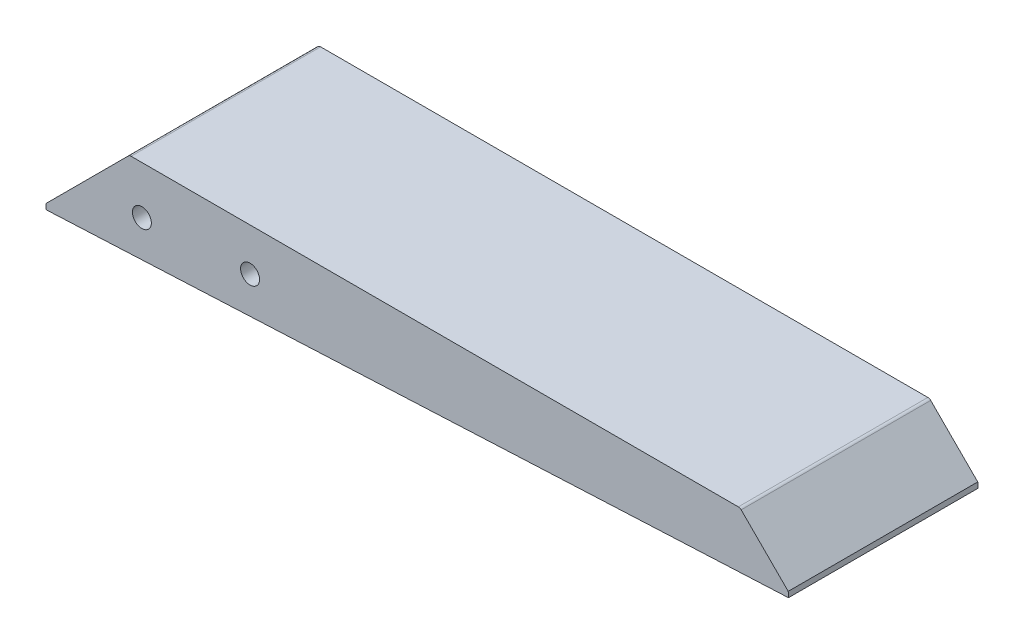
SolidWorks part; units mm, degrees
ref_plane "前视基准面" through (0, 0, 0) normal (0, 0, 1) x (1, 0, 0)
ref_plane "上视基准面" through (0, 0, 0) normal (0, 1, 0) x (1, 0, 0)
ref_plane "右视基准面" through (0, 0, 0) normal (1, 0, 0) x (0, 0, -1)
other "Configuration Table"
sketch "草图1" plane through (0, 0, 0) normal (0, 0, 1) x (1, 0, 0)
  line L0 (166.8324, 7.5944) -> (168.9537, 9.7157) construction
  line L1 (168.9537, 9.7157) -> (160.2639, 18.4056) construction
  line L2 (158.1425, 16.2843) -> (166.8324, 7.5944) construction
  line L3 (157.6217, 19.5) -> (45.4745, 19.5) construction
  line L4 (45.4745, 16.5) -> (157.6217, 16.5) construction
  line L5 (29.7639, 1.0944) -> (44.9537, 16.2843) construction
  line L6 (42.8324, 18.4056) -> (27.6425, 3.2157) construction
  line L7 (27.6425, 3.2157) -> (29.7639, 1.0944) construction
  line L8 (166.8324, 7.5944) -> (168.9537, 9.7157)
  line L9 (168.9537, 9.7157) -> (160.2639, 18.4056)
  line L10 (158.1425, 16.2843) -> (166.8324, 7.5944)
  line L11 (157.6217, 19.5) -> (45.4745, 19.5)
  line L12 (45.4745, 16.5) -> (157.6217, 16.5)
  line L13 (29.7639, 1.0944) -> (44.9537, 16.2843)
  line L14 (42.8324, 18.4056) -> (27.6425, 3.2157)
  line L15 (27.6425, 3.2157) -> (29.7639, 1.0944)
  line L16 (29.7639, 1.0944) -> (166.8324, 7.5944)
  arc A0 (158.1425, 16.2843) -> (157.6217, 16.5) centre (157.6217, 15.7634) ccw construction
  arc A1 (160.2639, 18.4056) -> (157.6217, 19.5) centre (157.6217, 15.7634) ccw construction
  arc A2 (45.4745, 16.5) -> (44.9537, 16.2843) centre (45.4745, 15.7634) ccw construction
  arc A3 (45.4745, 19.5) -> (42.8324, 18.4056) centre (45.4745, 15.7634) ccw construction
  arc A4 (158.1425, 16.2843) -> (157.6217, 16.5) centre (157.6217, 15.7634) ccw
  arc A5 (160.2639, 18.4056) -> (157.6217, 19.5) centre (157.6217, 15.7634) ccw
  arc A6 (45.4745, 16.5) -> (44.9537, 16.2843) centre (45.4745, 15.7634) ccw
  arc A7 (45.4745, 19.5) -> (42.8324, 18.4056) centre (45.4745, 15.7634) ccw
extrude "凸台-拉伸1" add sketch "草图1" against normal blind 35 contours L12 A6 L13 L16 L10 A4 region at (94.8139, 10.1061, 0)
sketch "草图2" plane through (0.015, -0.3163, 0) normal (0.0474, -0.9989, 0) x (0.9989, 0.0474, 0)
  line L0 (165.5048, -1.5) -> (31.2823, -1.5)
  line L1 (31.2823, -1.5) -> (31.2823, -33.5)
  line L2 (31.2823, -33.5) -> (165.5048, -33.5)
  line L3 (165.5048, -33.5) -> (165.5048, -1.5)
  line L4 (167.0048, 0) -> (29.7823, 0)
  line L5 (29.7823, 0) -> (29.7823, -35)
  line L6 (29.7823, -35) -> (167.0048, -35)
  line L7 (167.0048, -35) -> (167.0048, 0)
  line L8 (167.0048, 0) -> (29.7823, 0)
  line L9 (29.7823, 0) -> (29.7823, -35)
  line L10 (29.7823, -35) -> (167.0048, -35)
  line L11 (167.0048, -35) -> (167.0048, 0)
  dimension "D1" = 0
  dimension "D2" = 1.5
extrude "凸台-拉伸2" add sketch "草图2" along normal blind 1
fillet "圆角1" radius 2 4 edges at (31.2859, 0.666, -33.5) (165.3577, 7.0239, -33.5) (165.3577, 7.0239, -1.5) (31.2859, 0.666, -1.5)
sketch "草图3" plane through (0, 0, 0) normal (0, 0, 1) x (1, 0, 0)
  line L0 (166.8797, 6.5955) -> (29.8112, 0.0955) construction
  line L1 (29.8112, 0.0955) -> (29.7639, 1.0944) construction
  circle A0 centre (47.4713, 7.6906) radius 1.75
  circle A1 centre (67.4487, 8.6414) radius 1.75
  dimension "D1" = 3.5
  dimension "D3" = 20
  dimension "D4" = 6.75
  dimension "D5" = 18
  dimension "D2" = 2
extrude "切除-拉伸1" cut sketch "草图3" against normal blind 6.2
sketch "草图4" plane through (0, 0, -35) normal (0, 0, -1) x (-1, 0, 0)
  circle A0 centre (-47.4713, 7.6906) radius 1.75 construction
  circle A1 centre (-67.4487, 8.6414) radius 1.75 construction
  circle A2 centre (-47.4713, 7.6906) radius 1.75
  circle A3 centre (-67.4487, 8.6414) radius 1.75
extrude "切除-拉伸2" cut sketch "草图4" against normal blind 6.55
sketch "草图6" plane through (0.015, -0.3163, 0) normal (0.0474, -0.9989, 0) x (0.9989, 0.0474, 0)
  line L1199 (144.5332, -18.3417) -> (144.2984, -18.2008)
  line L1200 (144.2984, -18.2008) -> (143.9227, -18.2947)
  line L1201 (143.9227, -18.2947) -> (142.7956, -19.4688)
  line L1202 (142.7956, -19.4688) -> (142.279, -19.8915)
  line L1203 (142.279, -19.8915) -> (142.1381, -19.8915)
  line L1204 (142.1381, -19.8915) -> (142.0911, -19.7506)
  line L1205 (142.0911, -19.7506) -> (142.6547, -18.2478)
  line L1206 (142.6547, -18.2478) -> (142.7016, -17.8251)
  line L1207 (142.7016, -17.8251) -> (142.4668, -17.4963)
  line L1208 (142.4668, -17.4963) -> (141.9972, -17.4494)
  line L1209 (141.9972, -17.4494) -> (141.6684, -17.7312)
  line L1210 (141.6684, -17.7312) -> (141.2457, -18.3887)
  line L1211 (141.2457, -18.3887) -> (140.2595, -19.3749)
  line L1212 (140.2595, -19.3749) -> (139.2263, -20.1263)
  line L1213 (139.2263, -20.1263) -> (138.8036, -20.3142)
  line L1214 (138.8036, -20.3142) -> (138.6157, -20.3142)
  line L1215 (138.6157, -20.3142) -> (138.5218, -20.2203)
  line L1216 (138.5218, -20.2203) -> (138.5218, -19.9854)
  line L1217 (138.5218, -19.9854) -> (138.6627, -19.6097)
  line L1218 (138.6627, -19.6097) -> (139.4611, -18.4356)
  line L1219 (139.4611, -18.4356) -> (139.4611, -18.1069)
  line L1220 (139.4611, -18.1069) -> (139.2732, -17.872)
  line L1221 (139.2732, -17.872) -> (139.0384, -17.7781)
  line L1222 (139.0384, -17.7781) -> (138.6627, -17.872)
  line L1223 (138.6627, -17.872) -> (138.0052, -18.6235)
  line L1224 (138.0052, -18.6235) -> (137.5825, -19.3279)
  line L1225 (137.5825, -19.3279) -> (137.3477, -20.1263)
  line L1226 (137.3477, -20.1263) -> (137.3477, -20.4081)
  line L1227 (137.3477, -20.4081) -> (137.4886, -20.7838)
  line L1228 (137.4886, -20.7838) -> (137.9113, -21.1595)
  line L1229 (137.9113, -21.1595) -> (138.1931, -21.2535)
  line L1230 (138.1931, -21.2535) -> (138.7566, -21.2535)
  line L1231 (138.7566, -21.2535) -> (139.6959, -20.8778)
  line L1232 (139.6959, -20.8778) -> (140.6352, -20.1733)
  line L1233 (140.6352, -20.1733) -> (140.7761, -20.2203)
  line L1234 (140.7761, -20.2203) -> (140.6352, -20.8308)
  line L1235 (140.6352, -20.8308) -> (140.5413, -20.9247)
  line L1236 (140.5413, -20.9247) -> (138.5218, -21.817)
  line L1237 (138.5218, -21.817) -> (137.9582, -22.1928)
  line L1238 (137.9582, -22.1928) -> (137.6295, -22.5215)
  line L1239 (137.6295, -22.5215) -> (137.4416, -22.8503)
  line L1240 (137.4416, -22.8503) -> (137.4416, -23.2729)
  line L1241 (137.4416, -23.2729) -> (137.6765, -23.6487)
  line L1242 (137.6765, -23.6487) -> (138.0052, -23.8835)
  line L1243 (138.0052, -23.8835) -> (138.3809, -24.0244)
  line L1244 (138.3809, -24.0244) -> (139.1793, -24.0713)
  line L1245 (139.1793, -24.0713) -> (139.8368, -23.8835)
  line L1246 (139.8368, -23.8835) -> (140.4473, -23.5078)
  line L1247 (140.4473, -23.5078) -> (141.0109, -22.8503)
  line L1248 (141.0109, -22.8503) -> (141.4806, -21.817)
  line L1249 (141.4806, -21.817) -> (141.6215, -21.3004)
  line L1250 (141.6215, -21.3004) -> (142.8425, -20.596)
  line L1251 (142.8425, -20.596) -> (143.7348, -19.8445)
  line L1252 (143.7348, -19.8445) -> (144.4863, -18.9522)
  line L1253 (144.4863, -18.9522) -> (144.5802, -18.7644)
  line L1254 (144.5802, -18.7644) -> (144.5332, -18.3417)
  line L1255 (140.2125, -21.9579) -> (140.2125, -22.0988)
  line L1256 (140.2125, -22.0988) -> (140.0247, -22.4745)
  line L1257 (140.0247, -22.4745) -> (139.555, -22.9912)
  line L1258 (139.555, -22.9912) -> (139.0854, -23.226)
  line L1259 (139.0854, -23.226) -> (138.6627, -23.226)
  line L1260 (138.6627, -23.226) -> (138.5218, -23.0851)
  line L1261 (138.5218, -23.0851) -> (138.5688, -22.8503)
  line L1262 (138.5688, -22.8503) -> (138.8036, -22.5685)
  line L1263 (138.8036, -22.5685) -> (140.0716, -21.911)
  line L1264 (140.0716, -21.911) -> (140.2125, -21.9579)
  line L1265 (156.9788, -14.8663) -> (156.744, -14.7254)
  line L1266 (156.744, -14.7254) -> (156.4152, -14.7254)
  line L1267 (156.4152, -14.7254) -> (156.1334, -14.9133)
  line L1268 (156.1334, -14.9133) -> (156.0395, -15.1481)
  line L1269 (156.0395, -15.1481) -> (155.9925, -16.0874)
  line L1270 (155.9925, -16.0874) -> (155.5698, -17.1676)
  line L1271 (155.5698, -17.1676) -> (154.7715, -18.3417)
  line L1272 (154.7715, -18.3417) -> (153.9731, -19.0462)
  line L1273 (153.9731, -19.0462) -> (153.6913, -18.9992)
  line L1274 (153.6913, -18.9992) -> (153.6913, -18.3417)
  line L1275 (153.6913, -18.3417) -> (153.8791, -17.7312)
  line L1276 (153.8791, -17.7312) -> (153.8791, -17.3085)
  line L1277 (153.8791, -17.3085) -> (153.6913, -17.0736)
  line L1278 (153.6913, -17.0736) -> (153.5034, -16.9797)
  line L1279 (153.5034, -16.9797) -> (153.2686, -16.9797)
  line L1280 (153.2686, -16.9797) -> (153.0338, -17.0736)
  line L1281 (153.0338, -17.0736) -> (152.8459, -17.2615)
  line L1282 (152.8459, -17.2615) -> (152.3763, -18.1069)
  line L1283 (152.3763, -18.1069) -> (151.39, -19.1401)
  line L1284 (151.39, -19.1401) -> (151.1082, -19.3279)
  line L1285 (151.1082, -19.3279) -> (150.9204, -19.281)
  line L1286 (150.9204, -19.281) -> (150.9673, -18.9053)
  line L1287 (150.9673, -18.9053) -> (151.2022, -18.2478)
  line L1288 (151.2022, -18.2478) -> (152.0006, -16.7919)
  line L1289 (152.0006, -16.7919) -> (151.9536, -16.3692)
  line L1290 (151.9536, -16.3692) -> (151.5779, -16.1344)
  line L1291 (151.5779, -16.1344) -> (151.2022, -16.2283)
  line L1292 (151.2022, -16.2283) -> (150.9204, -16.5101)
  line L1293 (150.9204, -16.5101) -> (150.122, -17.872)
  line L1294 (150.122, -17.872) -> (149.8872, -18.6235)
  line L1295 (149.8872, -18.6235) -> (149.0418, -19.4219)
  line L1296 (149.0418, -19.4219) -> (148.4782, -19.8445)
  line L1297 (148.4782, -19.8445) -> (148.2434, -19.9385)
  line L1298 (148.2434, -19.9385) -> (147.9616, -19.9385)
  line L1299 (147.9616, -19.9385) -> (147.7268, -19.7976)
  line L1300 (147.7268, -19.7976) -> (147.3511, -19.4219)
  line L1301 (147.3511, -19.4219) -> (147.3511, -19.281)
  line L1302 (147.3511, -19.281) -> (149.1827, -17.5433)
  line L1303 (149.1827, -17.5433) -> (149.2766, -17.3554)
  line L1304 (149.2766, -17.3554) -> (149.2766, -17.1206)
  line L1305 (149.2766, -17.1206) -> (149.0418, -16.8388)
  line L1306 (149.0418, -16.8388) -> (148.6661, -16.7919)
  line L1307 (148.6661, -16.7919) -> (148.3373, -16.9328)
  line L1308 (148.3373, -16.9328) -> (146.6466, -18.4826)
  line L1309 (146.6466, -18.4826) -> (146.5057, -18.4826)
  line L1310 (146.5057, -18.4826) -> (145.6604, -17.5433)
  line L1311 (145.6604, -17.5433) -> (145.1907, -17.4963)
  line L1312 (145.1907, -17.4963) -> (145.0029, -17.5903)
  line L1313 (145.0029, -17.5903) -> (144.815, -17.8251)
  line L1314 (144.815, -17.8251) -> (144.815, -18.1069)
  line L1315 (144.815, -18.1069) -> (145.7543, -19.281)
  line L1316 (145.7543, -19.281) -> (145.7543, -19.3749)
  line L1317 (145.7543, -19.3749) -> (144.1106, -21.2065)
  line L1318 (144.1106, -21.2065) -> (143.9227, -21.5822)
  line L1319 (143.9227, -21.5822) -> (143.9697, -21.864)
  line L1320 (143.9697, -21.864) -> (144.2515, -22.0988)
  line L1321 (144.2515, -22.0988) -> (144.5802, -22.0988)
  line L1322 (144.5802, -22.0988) -> (144.815, -22.0049)
  line L1323 (144.815, -22.0049) -> (146.4588, -20.2203)
  line L1324 (146.4588, -20.2203) -> (146.5997, -20.2203)
  line L1325 (146.5997, -20.2203) -> (147.0693, -20.6429)
  line L1326 (147.0693, -20.6429) -> (147.492, -20.8778)
  line L1327 (147.492, -20.8778) -> (148.2904, -20.9247)
  line L1328 (148.2904, -20.9247) -> (149.0888, -20.549)
  line L1329 (149.0888, -20.549) -> (149.7463, -19.9385)
  line L1330 (149.7463, -19.9385) -> (149.8872, -19.9385)
  line L1331 (149.8872, -19.9385) -> (150.169, -20.2672)
  line L1332 (150.169, -20.2672) -> (150.4038, -20.4081)
  line L1333 (150.4038, -20.4081) -> (150.9204, -20.4551)
  line L1334 (150.9204, -20.4551) -> (151.2491, -20.3611)
  line L1335 (151.2491, -20.3611) -> (151.8127, -20.0324)
  line L1336 (151.8127, -20.0324) -> (152.5172, -19.3749)
  line L1337 (152.5172, -19.3749) -> (152.6581, -19.4219)
  line L1338 (152.6581, -19.4219) -> (152.752, -19.6567)
  line L1339 (152.752, -19.6567) -> (153.0338, -19.9385)
  line L1340 (153.0338, -19.9385) -> (153.4565, -20.1263)
  line L1341 (153.4565, -20.1263) -> (154.067, -20.0794)
  line L1342 (154.067, -20.0794) -> (154.5366, -19.8915)
  line L1343 (154.5366, -19.8915) -> (155.2881, -19.3279)
  line L1344 (155.2881, -19.3279) -> (155.7577, -18.8583)
  line L1345 (155.7577, -18.8583) -> (156.2743, -18.1538)
  line L1346 (156.2743, -18.1538) -> (156.744, -17.3085)
  line L1347 (156.744, -17.3085) -> (157.1197, -16.0404)
  line L1348 (157.1197, -16.0404) -> (157.1197, -15.1951)
  line L1349 (157.1197, -15.1951) -> (156.9788, -14.8663)
  line L1599 (103.178, -10.8157) -> (102.5205, -10.4869)
  line L1600 (102.5205, -10.4869) -> (101.7221, -10.2521)
  line L1601 (101.7221, -10.2521) -> (100.2192, -10.2521)
  line L1602 (100.2192, -10.2521) -> (99.5148, -10.5339)
  line L1603 (99.5148, -10.5339) -> (99.0921, -10.8626)
  line L1604 (99.0921, -10.8626) -> (97.4014, -11.6141)
  line L1605 (97.4014, -11.6141) -> (95.8985, -12.1307)
  line L1606 (95.8985, -12.1307) -> (94.8653, -12.2716)
  line L1607 (94.8653, -12.2716) -> (94.6305, -12.4594)
  line L1608 (94.6305, -12.4594) -> (94.5365, -12.6473)
  line L1609 (94.5365, -12.6473) -> (94.5835, -12.9291)
  line L1610 (94.5835, -12.9291) -> (95.0531, -13.3987)
  line L1611 (95.0531, -13.3987) -> (95.4289, -13.5866)
  line L1612 (95.4289, -13.5866) -> (96.0864, -13.7744)
  line L1613 (96.0864, -13.7744) -> (97.6362, -13.7744)
  line L1614 (97.6362, -13.7744) -> (97.824, -14.1032)
  line L1615 (97.824, -14.1032) -> (97.871, -14.9955)
  line L1616 (97.871, -14.9955) -> (97.7771, -15.3242)
  line L1617 (97.7771, -15.3242) -> (96.556, -15.7939)
  line L1618 (96.556, -15.7939) -> (95.8046, -16.2635)
  line L1619 (95.8046, -16.2635) -> (94.9592, -15.9817)
  line L1620 (94.9592, -15.9817) -> (94.4896, -15.9817)
  line L1621 (94.4896, -15.9817) -> (94.1608, -16.1226)
  line L1622 (94.1608, -16.1226) -> (94.0199, -16.2635)
  line L1623 (94.0199, -16.2635) -> (93.926, -16.5453)
  line L1624 (93.926, -16.5453) -> (94.2078, -17.4846)
  line L1625 (94.2078, -17.4846) -> (94.2548, -18.8935)
  line L1626 (94.2548, -18.8935) -> (94.3956, -19.7389)
  line L1627 (94.3956, -19.7389) -> (94.6305, -20.3964)
  line L1628 (94.6305, -20.3964) -> (94.9123, -20.866)
  line L1629 (94.9123, -20.866) -> (95.4758, -21.4296)
  line L1630 (95.4758, -21.4296) -> (95.9924, -21.6644)
  line L1631 (95.9924, -21.6644) -> (96.603, -21.7114)
  line L1632 (96.603, -21.7114) -> (97.3544, -21.4766)
  line L1633 (97.3544, -21.4766) -> (97.5423, -21.4766)
  line L1634 (97.5423, -21.4766) -> (97.5892, -21.6644)
  line L1635 (97.5892, -21.6644) -> (97.4483, -22.3219)
  line L1636 (97.4483, -22.3219) -> (97.2605, -22.7916)
  line L1637 (97.2605, -22.7916) -> (96.7908, -23.3551)
  line L1638 (96.7908, -23.3551) -> (95.1471, -23.8248)
  line L1639 (95.1471, -23.8248) -> (93.6442, -24.1066)
  line L1640 (93.6442, -24.1066) -> (92.7519, -24.1535)
  line L1641 (92.7519, -24.1535) -> (92.4701, -24.2944)
  line L1642 (92.4701, -24.2944) -> (92.1883, -24.6232)
  line L1643 (92.1883, -24.6232) -> (92.0944, -25.0928)
  line L1644 (92.0944, -25.0928) -> (92.3292, -25.6564)
  line L1645 (92.3292, -25.6564) -> (92.7519, -26.0791)
  line L1646 (92.7519, -26.0791) -> (93.4094, -26.4548)
  line L1647 (93.4094, -26.4548) -> (93.973, -26.6426)
  line L1648 (93.973, -26.6426) -> (95.5228, -26.6426)
  line L1649 (95.5228, -26.6426) -> (96.4621, -26.4078)
  line L1650 (96.4621, -26.4078) -> (100.5949, -24.905)
  line L1651 (100.5949, -24.905) -> (102.9431, -24.2005)
  line L1652 (102.9431, -24.2005) -> (103.3658, -24.2475)
  line L1653 (103.3658, -24.2475) -> (103.9764, -25.2807)
  line L1654 (103.9764, -25.2807) -> (104.446, -25.7034)
  line L1655 (104.446, -25.7034) -> (104.9156, -25.9382)
  line L1656 (104.9156, -25.9382) -> (105.3853, -26.0321)
  line L1657 (105.3853, -26.0321) -> (105.9019, -25.9851)
  line L1658 (105.9019, -25.9851) -> (106.4185, -25.7503)
  line L1659 (106.4185, -25.7503) -> (106.7942, -25.3746)
  line L1660 (106.7942, -25.3746) -> (107.029, -24.7641)
  line L1661 (107.029, -24.7641) -> (107.029, -24.2005)
  line L1662 (107.029, -24.2005) -> (106.8881, -23.6839)
  line L1663 (106.8881, -23.6839) -> (106.5594, -23.1203)
  line L1664 (106.5594, -23.1203) -> (105.8549, -22.3689)
  line L1665 (105.8549, -22.3689) -> (104.9156, -21.7114)
  line L1666 (104.9156, -21.7114) -> (103.8824, -21.2417)
  line L1667 (103.8824, -21.2417) -> (103.178, -21.0539)
  line L1668 (103.178, -21.0539) -> (102.6144, -21.1009)
  line L1669 (102.6144, -21.1009) -> (102.4265, -21.1948)
  line L1670 (102.4265, -21.1948) -> (102.2387, -21.4766)
  line L1671 (102.2387, -21.4766) -> (102.3326, -21.8523)
  line L1672 (102.3326, -21.8523) -> (102.6144, -22.181)
  line L1673 (102.6144, -22.181) -> (102.5205, -22.3689)
  line L1674 (102.5205, -22.3689) -> (101.2524, -22.5567)
  line L1675 (101.2524, -22.5567) -> (100.2662, -22.7916)
  line L1676 (100.2662, -22.7916) -> (99.9374, -22.7446)
  line L1677 (99.9374, -22.7446) -> (99.9374, -22.6037)
  line L1678 (99.9374, -22.6037) -> (100.2662, -21.9462)
  line L1679 (100.2662, -21.9462) -> (100.5949, -20.7721)
  line L1680 (100.5949, -20.7721) -> (100.7358, -20.6782)
  line L1681 (100.7358, -20.6782) -> (101.5342, -20.4903)
  line L1682 (101.5342, -20.4903) -> (102.8492, -20.3494)
  line L1683 (102.8492, -20.3494) -> (103.5067, -20.1146)
  line L1684 (103.5067, -20.1146) -> (103.8355, -19.7859)
  line L1685 (103.8355, -19.7859) -> (103.9764, -19.4571)
  line L1686 (103.9764, -19.4571) -> (104.5399, -18.6587)
  line L1687 (104.5399, -18.6587) -> (105.3383, -17.015)
  line L1688 (105.3383, -17.015) -> (105.3383, -16.3575)
  line L1689 (105.3383, -16.3575) -> (105.2444, -16.0757)
  line L1690 (105.2444, -16.0757) -> (105.0096, -15.7)
  line L1691 (105.0096, -15.7) -> (104.1642, -14.9955)
  line L1692 (104.1642, -14.9955) -> (103.6006, -14.7137)
  line L1693 (103.6006, -14.7137) -> (102.5674, -14.4319)
  line L1694 (102.5674, -14.4319) -> (101.5812, -14.4319)
  line L1695 (101.5812, -14.4319) -> (101.2524, -14.5259)
  line L1696 (101.2524, -14.5259) -> (100.8298, -14.4789)
  line L1697 (100.8298, -14.4789) -> (100.7828, -13.9623)
  line L1698 (100.7828, -13.9623) -> (100.6889, -13.7744)
  line L1699 (100.6889, -13.7744) -> (100.6889, -13.6335)
  line L1700 (100.6889, -13.6335) -> (100.7828, -13.5396)
  line L1701 (100.7828, -13.5396) -> (103.2249, -12.9291)
  line L1702 (103.2249, -12.9291) -> (103.7885, -12.4594)
  line L1703 (103.7885, -12.4594) -> (103.9294, -12.1307)
  line L1704 (103.9294, -12.1307) -> (103.8824, -11.6141)
  line L1705 (103.8824, -11.6141) -> (103.7415, -11.3323)
  line L1706 (103.7415, -11.3323) -> (103.178, -10.8157)
  line L1707 (97.7301, -17.2967) -> (97.7301, -19.3162)
  line L1708 (97.7301, -19.3162) -> (97.4014, -19.551)
  line L1709 (97.4014, -19.551) -> (96.8848, -19.598)
  line L1710 (96.8848, -19.598) -> (96.6969, -19.4571)
  line L1711 (96.6969, -19.4571) -> (96.556, -19.0344)
  line L1712 (96.556, -19.0344) -> (96.509, -17.9073)
  line L1713 (96.509, -17.9073) -> (96.6499, -17.7664)
  line L1714 (96.6499, -17.7664) -> (97.5892, -17.2967)
  line L1715 (97.5892, -17.2967) -> (97.7301, -17.2967)
  line L1716 (101.816, -16.3575) -> (102.0508, -16.5453)
  line L1717 (102.0508, -16.5453) -> (102.0978, -16.6862)
  line L1718 (102.0978, -16.6862) -> (102.0508, -17.0619)
  line L1719 (102.0508, -17.0619) -> (101.863, -17.5785)
  line L1720 (101.863, -17.5785) -> (101.3933, -18.3769)
  line L1721 (101.3933, -18.3769) -> (101.0646, -18.6118)
  line L1722 (101.0646, -18.6118) -> (100.7828, -18.6587)
  line L1723 (100.7828, -18.6587) -> (100.7358, -18.1891)
  line L1724 (100.7358, -18.1891) -> (100.8298, -16.5923)
  line L1725 (100.8298, -16.5923) -> (100.9237, -16.4984)
  line L1726 (100.9237, -16.4984) -> (101.2524, -16.4044)
  line L1727 (101.2524, -16.4044) -> (101.816, -16.3575)
  line L1728 (128.0221, -9.9703) -> (127.5524, -9.9234)
  line L1729 (127.5524, -9.9234) -> (126.9419, -10.2991)
  line L1730 (126.9419, -10.2991) -> (124.7815, -12.4594)
  line L1731 (124.7815, -12.4594) -> (124.6406, -12.4594)
  line L1732 (124.6406, -12.4594) -> (123.2787, -10.8626)
  line L1733 (123.2787, -10.8626) -> (122.9969, -10.7218)
  line L1734 (122.9969, -10.7218) -> (122.7151, -10.7218)
  line L1735 (122.7151, -10.7218) -> (122.3394, -10.9566)
  line L1736 (122.3394, -10.9566) -> (122.2455, -11.3323)
  line L1737 (122.2455, -11.3323) -> (122.3864, -11.661)
  line L1738 (122.3864, -11.661) -> (123.7483, -13.3987)
  line L1739 (123.7483, -13.3987) -> (123.7483, -13.5396)
  line L1740 (123.7483, -13.5396) -> (122.1515, -15.4182)
  line L1741 (122.1515, -15.4182) -> (121.541, -16.3105)
  line L1742 (121.541, -16.3105) -> (121.3062, -16.7801)
  line L1743 (121.3062, -16.7801) -> (121.3062, -17.1559)
  line L1744 (121.3062, -17.1559) -> (121.4471, -17.3907)
  line L1745 (121.4471, -17.3907) -> (121.7289, -17.5316)
  line L1746 (121.7289, -17.5316) -> (122.0106, -17.5316)
  line L1747 (122.0106, -17.5316) -> (122.2455, -17.4376)
  line L1748 (122.2455, -17.4376) -> (122.4803, -17.2028)
  line L1749 (122.4803, -17.2028) -> (123.1378, -16.2166)
  line L1750 (123.1378, -16.2166) -> (124.5937, -14.4789)
  line L1751 (124.5937, -14.4789) -> (124.7346, -14.4789)
  line L1752 (124.7346, -14.4789) -> (125.439, -15.0894)
  line L1753 (125.439, -15.0894) -> (125.9556, -15.4182)
  line L1754 (125.9556, -15.4182) -> (126.4253, -15.4651)
  line L1755 (126.4253, -15.4651) -> (126.754, -15.2773)
  line L1756 (126.754, -15.2773) -> (126.848, -15.0894)
  line L1757 (126.848, -15.0894) -> (126.801, -14.7137)
  line L1758 (126.801, -14.7137) -> (125.5799, -13.5396)
  line L1759 (125.5799, -13.5396) -> (125.5799, -13.4457)
  line L1760 (125.5799, -13.4457) -> (128.069, -10.8626)
  line L1761 (128.069, -10.8626) -> (128.2569, -10.5339)
  line L1762 (128.2569, -10.5339) -> (128.2569, -10.2991)
  line L1763 (128.2569, -10.2991) -> (128.0221, -9.9703)
  line L1764 (132.2489, -9.5476) -> (131.8262, -9.4067)
  line L1765 (131.8262, -9.4067) -> (131.4505, -9.4067)
  line L1766 (131.4505, -9.4067) -> (130.9339, -9.5476)
  line L1767 (130.9339, -9.5476) -> (130.4642, -9.8294)
  line L1768 (130.4642, -9.8294) -> (130.3233, -9.8294)
  line L1769 (130.3233, -9.8294) -> (130.2764, -9.4067)
  line L1770 (130.2764, -9.4067) -> (129.9476, -9.078)
  line L1771 (129.9476, -9.078) -> (129.5719, -9.078)
  line L1772 (129.5719, -9.078) -> (129.384, -9.1719)
  line L1773 (129.384, -9.1719) -> (129.1962, -9.4067)
  line L1774 (129.1962, -9.4067) -> (128.2099, -12.1776)
  line L1775 (128.2099, -12.1776) -> (127.3646, -15.2773)
  line L1776 (127.3646, -15.2773) -> (126.848, -18.0012)
  line L1777 (126.848, -18.0012) -> (126.848, -18.6118)
  line L1778 (126.848, -18.6118) -> (127.0828, -18.9405)
  line L1779 (127.0828, -18.9405) -> (127.5055, -19.0344)
  line L1780 (127.5055, -19.0344) -> (127.7403, -18.9405)
  line L1781 (127.7403, -18.9405) -> (127.9751, -18.6587)
  line L1782 (127.9751, -18.6587) -> (128.2099, -17.1089)
  line L1783 (128.2099, -17.1089) -> (128.7735, -14.7607)
  line L1784 (128.7735, -14.7607) -> (129.6189, -14.7137)
  line L1785 (129.6189, -14.7137) -> (130.5112, -14.2441)
  line L1786 (130.5112, -14.2441) -> (130.8869, -13.9623)
  line L1787 (130.8869, -13.9623) -> (131.6853, -13.1639)
  line L1788 (131.6853, -13.1639) -> (132.3898, -12.1307)
  line L1789 (132.3898, -12.1307) -> (132.7185, -11.2853)
  line L1790 (132.7185, -11.2853) -> (132.8124, -10.5339)
  line L1791 (132.8124, -10.5339) -> (132.6246, -9.9234)
  line L1792 (132.6246, -9.9234) -> (132.2489, -9.5476)
  line L1793 (131.5444, -10.44) -> (131.6383, -10.6748)
  line L1794 (131.6383, -10.6748) -> (131.5914, -11.0035)
  line L1795 (131.5914, -11.0035) -> (131.4505, -11.4262)
  line L1796 (131.4505, -11.4262) -> (130.9808, -12.2246)
  line L1797 (130.9808, -12.2246) -> (130.0885, -13.2109)
  line L1798 (130.0885, -13.2109) -> (129.6658, -13.5396)
  line L1799 (129.6658, -13.5396) -> (129.1962, -13.7275)
  line L1800 (129.1962, -13.7275) -> (129.1492, -13.4926)
  line L1801 (129.1492, -13.4926) -> (129.431, -12.7412)
  line L1802 (129.431, -12.7412) -> (130.0415, -11.661)
  line L1803 (130.0415, -11.661) -> (130.8399, -10.7687)
  line L1804 (130.8399, -10.7687) -> (131.3565, -10.44)
  line L1805 (131.3565, -10.44) -> (131.5444, -10.44)
  line L1806 (46.3512, -7.6691) -> (46.2103, -8.0448)
  line L1807 (46.2103, -8.0448) -> (46.2103, -8.3266)
  line L1808 (46.2103, -8.3266) -> (46.4921, -8.8901)
  line L1809 (46.4921, -8.8901) -> (47.0556, -9.4537)
  line L1810 (47.0556, -9.4537) -> (48.6524, -10.6748)
  line L1811 (48.6524, -10.6748) -> (48.5115, -11.2384)
  line L1812 (48.5115, -11.2384) -> (47.8071, -12.7412)
  line L1813 (47.8071, -12.7412) -> (47.8071, -13.023)
  line L1814 (47.8071, -13.023) -> (47.9949, -13.2109)
  line L1815 (47.9949, -13.2109) -> (48.4176, -13.2109)
  line L1816 (48.4176, -13.2109) -> (49.3569, -12.5534)
  line L1817 (49.3569, -12.5534) -> (50.3431, -12.0368)
  line L1818 (50.3431, -12.0368) -> (50.8128, -11.8959)
  line L1819 (50.8128, -11.8959) -> (51.3764, -11.8959)
  line L1820 (51.3764, -11.8959) -> (51.9399, -11.755)
  line L1821 (51.9399, -11.755) -> (52.5974, -11.3792)
  line L1822 (52.5974, -11.3792) -> (52.9262, -11.0505)
  line L1823 (52.9262, -11.0505) -> (53.161, -10.6748)
  line L1824 (53.161, -10.6748) -> (53.3019, -10.0173)
  line L1825 (53.3019, -10.0173) -> (53.161, -9.4537)
  line L1826 (53.161, -9.4537) -> (52.9731, -9.125)
  line L1827 (52.9731, -9.125) -> (52.4565, -8.5614)
  line L1828 (52.4565, -8.5614) -> (52.0808, -8.2796)
  line L1829 (52.0808, -8.2796) -> (50.9537, -7.6691)
  line L1830 (50.9537, -7.6691) -> (49.8735, -7.2934)
  line L1831 (49.8735, -7.2934) -> (48.6524, -7.0585)
  line L1832 (48.6524, -7.0585) -> (47.1965, -7.1055)
  line L1833 (47.1965, -7.1055) -> (46.7269, -7.2934)
  line L1834 (46.7269, -7.2934) -> (46.3512, -7.6691)
  line L1835 (154.2281, -7.4342) -> (154.0403, -7.1994)
  line L1836 (154.0403, -7.1994) -> (153.6646, -7.1994)
  line L1837 (153.6646, -7.1994) -> (152.0678, -8.2796)
  line L1838 (152.0678, -8.2796) -> (151.5042, -8.5144)
  line L1839 (151.5042, -8.5144) -> (151.1755, -8.5614)
  line L1840 (151.1755, -8.5614) -> (151.0815, -8.4675)
  line L1841 (151.0815, -8.4675) -> (151.0815, -8.3266)
  line L1842 (151.0815, -8.3266) -> (151.5042, -7.0116)
  line L1843 (151.5042, -7.0116) -> (151.4573, -6.495)
  line L1844 (151.4573, -6.495) -> (151.2224, -6.2132)
  line L1845 (151.2224, -6.2132) -> (150.9876, -6.1193)
  line L1846 (150.9876, -6.1193) -> (150.518, -6.1662)
  line L1847 (150.518, -6.1662) -> (150.0014, -6.448)
  line L1848 (150.0014, -6.448) -> (149.2969, -7.0585)
  line L1849 (149.2969, -7.0585) -> (149.156, -7.0116)
  line L1850 (149.156, -7.0116) -> (149.109, -6.6359)
  line L1851 (149.109, -6.6359) -> (148.9212, -6.448)
  line L1852 (148.9212, -6.448) -> (148.4515, -6.401)
  line L1853 (148.4515, -6.401) -> (148.2167, -6.5419)
  line L1854 (148.2167, -6.5419) -> (148.0289, -6.8237)
  line L1855 (148.0289, -6.8237) -> (147.5123, -8.0448)
  line L1856 (147.5123, -8.0448) -> (146.7139, -8.8901)
  line L1857 (146.7139, -8.8901) -> (145.9624, -9.5476)
  line L1858 (145.9624, -9.5476) -> (145.8685, -9.5476)
  line L1859 (145.8685, -9.5476) -> (145.8215, -9.3128)
  line L1860 (145.8215, -9.3128) -> (146.573, -7.3873)
  line L1861 (146.573, -7.3873) -> (146.573, -7.1525)
  line L1862 (146.573, -7.1525) -> (146.3851, -6.8707)
  line L1863 (146.3851, -6.8707) -> (146.1973, -6.7767)
  line L1864 (146.1973, -6.7767) -> (145.9155, -6.7767)
  line L1865 (145.9155, -6.7767) -> (145.7276, -6.8707)
  line L1866 (145.7276, -6.8707) -> (145.4928, -7.1525)
  line L1867 (145.4928, -7.1525) -> (144.7883, -8.7492)
  line L1868 (144.7883, -8.7492) -> (144.6005, -9.5007)
  line L1869 (144.6005, -9.5007) -> (144.6005, -10.2051)
  line L1870 (144.6005, -10.2051) -> (144.9292, -10.6748)
  line L1871 (144.9292, -10.6748) -> (145.258, -10.8157)
  line L1872 (145.258, -10.8157) -> (145.5398, -10.8157)
  line L1873 (145.5398, -10.8157) -> (146.0564, -10.6278)
  line L1874 (146.0564, -10.6278) -> (147.0896, -9.7825)
  line L1875 (147.0896, -9.7825) -> (147.2305, -9.7825)
  line L1876 (147.2305, -9.7825) -> (147.3244, -9.9703)
  line L1877 (147.3244, -9.9703) -> (147.5123, -10.1112)
  line L1878 (147.5123, -10.1112) -> (147.9819, -10.1112)
  line L1879 (147.9819, -10.1112) -> (148.3576, -9.7825)
  line L1880 (148.3576, -9.7825) -> (148.7333, -9.2189)
  line L1881 (148.7333, -9.2189) -> (149.8135, -7.9509)
  line L1882 (149.8135, -7.9509) -> (149.9544, -7.9978)
  line L1883 (149.9544, -7.9978) -> (149.9074, -8.7962)
  line L1884 (149.9074, -8.7962) -> (150.0014, -9.078)
  line L1885 (150.0014, -9.078) -> (150.2362, -9.3598)
  line L1886 (150.2362, -9.3598) -> (150.7998, -9.5946)
  line L1887 (150.7998, -9.5946) -> (151.6451, -9.5007)
  line L1888 (151.6451, -9.5007) -> (152.6314, -9.078)
  line L1889 (152.6314, -9.078) -> (153.5237, -8.5144)
  line L1890 (153.5237, -8.5144) -> (153.9464, -8.1387)
  line L1891 (153.9464, -8.1387) -> (154.2281, -7.763)
  line L1892 (154.2281, -7.763) -> (154.2281, -7.4342)
  line L1893 (132.8594, -12.8821) -> (133.0003, -13.2109)
  line L1894 (133.0003, -13.2109) -> (133.2351, -13.4457)
  line L1895 (133.2351, -13.4457) -> (133.5639, -13.5866)
  line L1896 (133.5639, -13.5866) -> (133.8926, -13.5866)
  line L1897 (133.8926, -13.5866) -> (134.644, -13.2109)
  line L1898 (134.644, -13.2109) -> (135.5364, -12.3185)
  line L1899 (135.5364, -12.3185) -> (135.6303, -12.3185)
  line L1900 (135.6303, -12.3185) -> (135.7712, -12.5064)
  line L1901 (135.7712, -12.5064) -> (136.006, -12.6473)
  line L1902 (136.006, -12.6473) -> (136.5226, -12.6473)
  line L1903 (136.5226, -12.6473) -> (136.7574, -12.5534)
  line L1904 (136.7574, -12.5534) -> (137.0862, -12.3185)
  line L1905 (137.0862, -12.3185) -> (137.9315, -11.4262)
  line L1906 (137.9315, -11.4262) -> (138.0255, -11.4262)
  line L1907 (138.0255, -11.4262) -> (138.1664, -11.708)
  line L1908 (138.1664, -11.708) -> (138.4012, -11.8959)
  line L1909 (138.4012, -11.8959) -> (139.0117, -11.9428)
  line L1910 (139.0117, -11.9428) -> (139.6223, -11.5671)
  line L1911 (139.6223, -11.5671) -> (140.0449, -11.1444)
  line L1912 (140.0449, -11.1444) -> (140.7964, -10.2051)
  line L1913 (140.7964, -10.2051) -> (141.3599, -9.3598)
  line L1914 (141.3599, -9.3598) -> (142.0174, -9.6885)
  line L1915 (142.0174, -9.6885) -> (143.0976, -9.8294)
  line L1916 (143.0976, -9.8294) -> (143.1915, -10.0173)
  line L1917 (143.1915, -10.0173) -> (142.7689, -10.393)
  line L1918 (142.7689, -10.393) -> (142.0174, -10.6748)
  line L1919 (142.0174, -10.6748) -> (141.7356, -10.6748)
  line L1920 (141.7356, -10.6748) -> (141.4069, -10.393)
  line L1921 (141.4069, -10.393) -> (141.1721, -10.393)
  line L1922 (141.1721, -10.393) -> (140.9842, -10.4869)
  line L1923 (140.9842, -10.4869) -> (140.7964, -10.6748)
  line L1924 (140.7964, -10.6748) -> (140.7024, -10.9096)
  line L1925 (140.7024, -10.9096) -> (140.7024, -11.1444)
  line L1926 (140.7024, -11.1444) -> (140.7964, -11.3323)
  line L1927 (140.7964, -11.3323) -> (140.9842, -11.5201)
  line L1928 (140.9842, -11.5201) -> (141.5478, -11.708)
  line L1929 (141.5478, -11.708) -> (142.2992, -11.661)
  line L1930 (142.2992, -11.661) -> (143.1915, -11.3323)
  line L1931 (143.1915, -11.3323) -> (143.7081, -11.0035)
  line L1932 (143.7081, -11.0035) -> (144.1778, -10.5339)
  line L1933 (144.1778, -10.5339) -> (144.4126, -10.0642)
  line L1934 (144.4126, -10.0642) -> (144.4126, -9.7355)
  line L1935 (144.4126, -9.7355) -> (144.2248, -9.3128)
  line L1936 (144.2248, -9.3128) -> (143.943, -9.078)
  line L1937 (143.943, -9.078) -> (143.2855, -8.8432)
  line L1938 (143.2855, -8.8432) -> (142.534, -8.7492)
  line L1939 (142.534, -8.7492) -> (142.4871, -8.4675)
  line L1940 (142.4871, -8.4675) -> (143.0506, -7.9509)
  line L1941 (143.0506, -7.9509) -> (143.1915, -7.9978)
  line L1942 (143.1915, -7.9978) -> (143.2385, -8.2326)
  line L1943 (143.2385, -8.2326) -> (143.4264, -8.3735)
  line L1944 (143.4264, -8.3735) -> (143.849, -8.3266)
  line L1945 (143.849, -8.3266) -> (144.1308, -8.0918)
  line L1946 (144.1308, -8.0918) -> (144.4126, -7.6691)
  line L1947 (144.4126, -7.6691) -> (144.4596, -7.2934)
  line L1948 (144.4596, -7.2934) -> (144.3656, -7.0585)
  line L1949 (144.3656, -7.0585) -> (144.2248, -6.9176)
  line L1950 (144.2248, -6.9176) -> (143.896, -6.7767)
  line L1951 (143.896, -6.7767) -> (143.4264, -6.7767)
  line L1952 (143.4264, -6.7767) -> (142.8158, -6.9646)
  line L1953 (142.8158, -6.9646) -> (142.1583, -7.3403)
  line L1954 (142.1583, -7.3403) -> (141.4069, -8.0918)
  line L1955 (141.4069, -8.0918) -> (140.8903, -8.4675)
  line L1956 (140.8903, -8.4675) -> (139.2465, -10.5339)
  line L1957 (139.2465, -10.5339) -> (139.1056, -10.4869)
  line L1958 (139.1056, -10.4869) -> (139.1056, -10.346)
  line L1959 (139.1056, -10.346) -> (139.4344, -9.2189)
  line L1960 (139.4344, -9.2189) -> (139.4344, -8.7023)
  line L1961 (139.4344, -8.7023) -> (139.1526, -8.4205)
  line L1962 (139.1526, -8.4205) -> (138.683, -8.4675)
  line L1963 (138.683, -8.4675) -> (138.4481, -8.7023)
  line L1964 (138.4481, -8.7023) -> (138.0724, -9.5946)
  line L1965 (138.0724, -9.5946) -> (137.7437, -10.1112)
  line L1966 (137.7437, -10.1112) -> (136.8044, -11.2384)
  line L1967 (136.8044, -11.2384) -> (136.6635, -11.1914)
  line L1968 (136.6635, -11.1914) -> (136.6635, -11.0505)
  line L1969 (136.6635, -11.0505) -> (137.0392, -10.0642)
  line L1970 (137.0392, -10.0642) -> (137.274, -9.6416)
  line L1971 (137.274, -9.6416) -> (137.321, -9.125)
  line L1972 (137.321, -9.125) -> (137.0862, -8.8432)
  line L1973 (137.0862, -8.8432) -> (136.9453, -8.7962)
  line L1974 (136.9453, -8.7962) -> (136.5226, -8.8901)
  line L1975 (136.5226, -8.8901) -> (136.1469, -9.4067)
  line L1976 (136.1469, -9.4067) -> (135.7712, -10.1582)
  line L1977 (135.7712, -10.1582) -> (135.5364, -10.8626)
  line L1978 (135.5364, -10.8626) -> (135.0198, -11.4732)
  line L1979 (135.0198, -11.4732) -> (134.1274, -12.3655)
  line L1980 (134.1274, -12.3655) -> (134.0335, -12.3655)
  line L1981 (134.0335, -12.3655) -> (133.9865, -12.0837)
  line L1982 (133.9865, -12.0837) -> (134.0805, -11.5201)
  line L1983 (134.0805, -11.5201) -> (134.4092, -10.2991)
  line L1984 (134.4092, -10.2991) -> (135.4424, -7.81)
  line L1985 (135.4424, -7.81) -> (136.006, -6.0253)
  line L1986 (136.006, -6.0253) -> (136.006, -5.6966)
  line L1987 (136.006, -5.6966) -> (135.7712, -5.3678)
  line L1988 (135.7712, -5.3678) -> (135.2076, -5.3678)
  line L1989 (135.2076, -5.3678) -> (134.9258, -5.6496)
  line L1990 (134.9258, -5.6496) -> (134.5031, -6.401)
  line L1991 (134.5031, -6.401) -> (134.1274, -7.2464)
  line L1992 (134.1274, -7.2464) -> (133.4699, -9.125)
  line L1993 (133.4699, -9.125) -> (133.0473, -10.7218)
  line L1994 (133.0473, -10.7218) -> (132.8594, -11.755)
  line L1995 (132.8594, -11.755) -> (132.8594, -12.8821)
  line L1996 (146.9956, -4.8982) -> (146.573, -4.8982)
  line L1997 (146.573, -4.8982) -> (146.1033, -5.3209)
  line L1998 (146.1033, -5.3209) -> (145.8215, -5.9314)
  line L1999 (145.8215, -5.9314) -> (145.8685, -6.2601)
  line L2000 (145.8685, -6.2601) -> (146.0564, -6.495)
  line L2001 (146.0564, -6.495) -> (146.4321, -6.5889)
  line L2002 (146.4321, -6.5889) -> (146.7608, -6.448)
  line L2003 (146.7608, -6.448) -> (147.1365, -5.9314)
  line L2004 (147.1365, -5.9314) -> (147.3244, -5.3678)
  line L2005 (147.3244, -5.3678) -> (147.2305, -5.086)
  line L2006 (147.2305, -5.086) -> (146.9956, -4.8982)
  line L2007 (83.1712, -24.2944) -> (82.9833, -24.0126)
  line L2008 (82.9833, -24.0126) -> (82.7955, -23.9187)
  line L2009 (82.7955, -23.9187) -> (82.4198, -23.9187)
  line L2010 (82.4198, -23.9187) -> (76.0796, -25.1868)
  line L2011 (76.0796, -25.1868) -> (73.6844, -25.5625)
  line L2012 (73.6844, -25.5625) -> (71.1483, -25.8442)
  line L2013 (71.1483, -25.8442) -> (69.6455, -25.9382)
  line L2014 (69.6455, -25.9382) -> (67.1094, -25.9382)
  line L2015 (67.1094, -25.9382) -> (65.1839, -25.7973)
  line L2016 (65.1839, -25.7973) -> (64.7142, -25.7034)
  line L2017 (64.7142, -25.7034) -> (64.7612, -25.5625)
  line L2018 (64.7612, -25.5625) -> (65.2778, -25.5625)
  line L2019 (65.2778, -25.5625) -> (66.264, -25.1868)
  line L2020 (66.264, -25.1868) -> (67.2033, -24.3414)
  line L2021 (67.2033, -24.3414) -> (67.579, -23.8248)
  line L2022 (67.579, -23.8248) -> (68.0956, -22.7916)
  line L2023 (68.0956, -22.7916) -> (68.3774, -22.0401)
  line L2024 (68.3774, -22.0401) -> (68.7062, -20.7721)
  line L2025 (68.7062, -20.7721) -> (68.941, -19.3162)
  line L2026 (68.941, -19.3162) -> (69.1758, -19.3162)
  line L2027 (69.1758, -19.3162) -> (70.209, -19.7389)
  line L2028 (70.209, -19.7389) -> (71.7119, -20.4903)
  line L2029 (71.7119, -20.4903) -> (74.5767, -22.1341)
  line L2030 (74.5767, -22.1341) -> (75.9856, -22.6037)
  line L2031 (75.9856, -22.6037) -> (76.9719, -22.6037)
  line L2032 (76.9719, -22.6037) -> (77.6764, -22.3219)
  line L2033 (77.6764, -22.3219) -> (78.099, -21.9462)
  line L2034 (78.099, -21.9462) -> (78.3808, -21.3826)
  line L2035 (78.3808, -21.3826) -> (78.3808, -20.7721)
  line L2036 (78.3808, -20.7721) -> (78.2869, -20.4434)
  line L2037 (78.2869, -20.4434) -> (77.8173, -19.7389)
  line L2038 (77.8173, -19.7389) -> (77.3476, -19.3162)
  line L2039 (77.3476, -19.3162) -> (75.9856, -18.5178)
  line L2040 (75.9856, -18.5178) -> (74.3419, -17.9073)
  line L2041 (74.3419, -17.9073) -> (72.6512, -17.4846)
  line L2042 (72.6512, -17.4846) -> (70.5848, -17.1559)
  line L2043 (70.5848, -17.1559) -> (69.1289, -17.0619)
  line L2044 (69.1289, -17.0619) -> (68.894, -16.968)
  line L2045 (68.894, -16.968) -> (68.941, -16.8271)
  line L2046 (68.941, -16.8271) -> (70.8196, -16.1226)
  line L2047 (70.8196, -16.1226) -> (72.1815, -15.4182)
  line L2048 (72.1815, -15.4182) -> (73.3556, -14.6198)
  line L2049 (73.3556, -14.6198) -> (74.201, -13.7744)
  line L2050 (74.201, -13.7744) -> (74.4828, -13.2578)
  line L2051 (74.4828, -13.2578) -> (74.5298, -12.5064)
  line L2052 (74.5298, -12.5064) -> (74.248, -11.8959)
  line L2053 (74.248, -11.8959) -> (73.6844, -11.3792)
  line L2054 (73.6844, -11.3792) -> (73.2148, -11.1444)
  line L2055 (73.2148, -11.1444) -> (72.5573, -10.9566)
  line L2056 (72.5573, -10.9566) -> (71.524, -10.9566)
  line L2057 (71.524, -10.9566) -> (70.6787, -11.2384)
  line L2058 (70.6787, -11.2384) -> (70.3969, -11.6141)
  line L2059 (70.3969, -11.6141) -> (70.4908, -11.9428)
  line L2060 (70.4908, -11.9428) -> (70.6787, -12.1307)
  line L2061 (70.6787, -12.1307) -> (70.6787, -12.3655)
  line L2062 (70.6787, -12.3655) -> (70.5378, -12.6473)
  line L2063 (70.5378, -12.6473) -> (69.5985, -13.8214)
  line L2064 (69.5985, -13.8214) -> (69.0349, -14.385)
  line L2065 (69.0349, -14.385) -> (68.0956, -15.1364)
  line L2066 (68.0956, -15.1364) -> (67.9078, -15.0425)
  line L2067 (67.9078, -15.0425) -> (67.579, -14.5259)
  line L2068 (67.579, -14.5259) -> (66.6398, -13.6335)
  line L2069 (66.6398, -13.6335) -> (66.0762, -13.2578)
  line L2070 (66.0762, -13.2578) -> (65.1369, -12.8351)
  line L2071 (65.1369, -12.8351) -> (65.1369, -12.7412)
  line L2072 (65.1369, -12.7412) -> (66.5928, -11.3792)
  line L2073 (66.5928, -11.3792) -> (67.2503, -10.5809)
  line L2074 (67.2503, -10.5809) -> (67.4381, -10.1582)
  line L2075 (67.4381, -10.1582) -> (67.4381, -9.6416)
  line L2076 (67.4381, -9.6416) -> (67.1564, -9.125)
  line L2077 (67.1564, -9.125) -> (67.2033, -8.9841)
  line L2078 (67.2033, -8.9841) -> (70.5848, -7.763)
  line L2079 (70.5848, -7.763) -> (71.1483, -7.4812)
  line L2080 (71.1483, -7.4812) -> (71.571, -7.0585)
  line L2081 (71.571, -7.0585) -> (71.7589, -6.7298)
  line L2082 (71.7589, -6.7298) -> (71.7589, -5.8375)
  line L2083 (71.7589, -5.8375) -> (71.524, -5.4148)
  line L2084 (71.524, -5.4148) -> (70.9135, -4.8982)
  line L2085 (70.9135, -4.8982) -> (70.256, -4.6164)
  line L2086 (70.256, -4.6164) -> (69.7864, -4.5225)
  line L2087 (69.7864, -4.5225) -> (68.894, -4.5225)
  line L2088 (68.894, -4.5225) -> (68.1896, -4.6634)
  line L2089 (68.1896, -4.6634) -> (67.3912, -4.9451)
  line L2090 (67.3912, -4.9451) -> (62.7417, -7.1525)
  line L2091 (62.7417, -7.1525) -> (60.2526, -8.1857)
  line L2092 (60.2526, -8.1857) -> (57.9983, -8.8901)
  line L2093 (57.9983, -8.8901) -> (56.8712, -9.078)
  line L2094 (56.8712, -9.078) -> (56.3076, -9.078)
  line L2095 (56.3076, -9.078) -> (56.0258, -9.2189)
  line L2096 (56.0258, -9.2189) -> (55.8849, -9.4537)
  line L2097 (55.8849, -9.4537) -> (55.9789, -9.8294)
  line L2098 (55.9789, -9.8294) -> (56.4485, -10.2051)
  line L2099 (56.4485, -10.2051) -> (56.9181, -10.44)
  line L2100 (56.9181, -10.44) -> (57.8105, -10.6748)
  line L2101 (57.8105, -10.6748) -> (58.7498, -10.7687)
  line L2102 (58.7498, -10.7687) -> (59.9239, -10.7218)
  line L2103 (59.9239, -10.7218) -> (61.1919, -10.5339)
  line L2104 (61.1919, -10.5339) -> (61.8494, -10.346)
  line L2105 (61.8494, -10.346) -> (62.0373, -10.346)
  line L2106 (62.0373, -10.346) -> (62.0842, -10.5339)
  line L2107 (62.0842, -10.5339) -> (61.2858, -11.5201)
  line L2108 (61.2858, -11.5201) -> (60.0648, -12.7412)
  line L2109 (60.0648, -12.7412) -> (59.1255, -13.5396)
  line L2110 (59.1255, -13.5396) -> (57.9983, -14.385)
  line L2111 (57.9983, -14.385) -> (56.8712, -15.0894)
  line L2112 (56.8712, -15.0894) -> (56.0258, -15.5121)
  line L2113 (56.0258, -15.5121) -> (55.5092, -15.653)
  line L2114 (55.5092, -15.653) -> (55.3214, -15.7939)
  line L2115 (55.3214, -15.7939) -> (55.2274, -16.0757)
  line L2116 (55.2274, -16.0757) -> (55.4153, -16.3105)
  line L2117 (55.4153, -16.3105) -> (55.744, -16.4514)
  line L2118 (55.744, -16.4514) -> (56.3546, -16.4984)
  line L2119 (56.3546, -16.4984) -> (57.9514, -16.2635)
  line L2120 (57.9514, -16.2635) -> (58.8437, -16.0287)
  line L2121 (58.8437, -16.0287) -> (59.8299, -15.653)
  line L2122 (59.8299, -15.653) -> (60.0648, -15.7)
  line L2123 (60.0648, -15.7) -> (59.9708, -15.9817)
  line L2124 (59.9708, -15.9817) -> (59.6421, -16.3575)
  line L2125 (59.6421, -16.3575) -> (58.1392, -17.6725)
  line L2126 (58.1392, -17.6725) -> (56.4485, -18.8466)
  line L2127 (56.4485, -18.8466) -> (55.838, -19.1753)
  line L2128 (55.838, -19.1753) -> (55.3214, -19.3162)
  line L2129 (55.3214, -19.3162) -> (55.0865, -19.645)
  line L2130 (55.0865, -19.645) -> (55.1805, -19.9268)
  line L2131 (55.1805, -19.9268) -> (55.6501, -20.2555)
  line L2132 (55.6501, -20.2555) -> (56.1667, -20.3964)
  line L2133 (56.1667, -20.3964) -> (57.106, -20.3964)
  line L2134 (57.106, -20.3964) -> (57.5756, -20.3025)
  line L2135 (57.5756, -20.3025) -> (58.5149, -19.9737)
  line L2136 (58.5149, -19.9737) -> (59.3603, -19.551)
  line L2137 (59.3603, -19.551) -> (60.5344, -18.7526)
  line L2138 (60.5344, -18.7526) -> (61.6146, -17.8134)
  line L2139 (61.6146, -17.8134) -> (61.7555, -17.8134)
  line L2140 (61.7555, -17.8134) -> (61.8494, -17.9073)
  line L2141 (61.8494, -17.9073) -> (61.8964, -18.1421)
  line L2142 (61.8964, -18.1421) -> (61.4267, -18.8466)
  line L2143 (61.4267, -18.8466) -> (60.6283, -19.6919)
  line L2144 (60.6283, -19.6919) -> (58.7967, -21.1948)
  line L2145 (58.7967, -21.1948) -> (57.7165, -21.8992)
  line L2146 (57.7165, -21.8992) -> (56.2606, -22.6507)
  line L2147 (56.2606, -22.6507) -> (55.3214, -23.0264)
  line L2148 (55.3214, -23.0264) -> (54.476, -23.2612)
  line L2149 (54.476, -23.2612) -> (54.2881, -23.496)
  line L2150 (54.2881, -23.496) -> (54.3351, -23.6839)
  line L2151 (54.3351, -23.6839) -> (54.6639, -23.9187)
  line L2152 (54.6639, -23.9187) -> (55.1805, -24.0126)
  line L2153 (55.1805, -24.0126) -> (56.4015, -23.9187)
  line L2154 (56.4015, -23.9187) -> (58.2331, -23.543)
  line L2155 (58.2331, -23.543) -> (60.7223, -22.6507)
  line L2156 (60.7223, -22.6507) -> (61.098, -23.4021)
  line L2157 (61.098, -23.4021) -> (62.0842, -24.4823)
  line L2158 (62.0842, -24.4823) -> (62.9765, -25.0928)
  line L2159 (62.9765, -25.0928) -> (63.5871, -25.3746)
  line L2160 (63.5871, -25.3746) -> (64.0098, -25.4685)
  line L2161 (64.0098, -25.4685) -> (64.0098, -25.6564)
  line L2162 (64.0098, -25.6564) -> (54.2881, -24.2944)
  line L2163 (54.2881, -24.2944) -> (51.4703, -24.0596)
  line L2164 (51.4703, -24.0596) -> (51.4233, -23.9187)
  line L2165 (51.4233, -23.9187) -> (51.893, -23.59)
  line L2166 (51.893, -23.59) -> (52.4565, -22.9325)
  line L2167 (52.4565, -22.9325) -> (52.6444, -22.5098)
  line L2168 (52.6444, -22.5098) -> (52.6914, -21.9932)
  line L2169 (52.6914, -21.9932) -> (52.4565, -21.3357)
  line L2170 (52.4565, -21.3357) -> (51.3294, -19.8798)
  line L2171 (51.3294, -19.8798) -> (51.2355, -19.551)
  line L2172 (51.2355, -19.551) -> (51.2355, -19.0814)
  line L2173 (51.2355, -19.0814) -> (51.3294, -18.7526)
  line L2174 (51.3294, -18.7526) -> (51.7051, -18.0951)
  line L2175 (51.7051, -18.0951) -> (53.208, -16.4514)
  line L2176 (53.208, -16.4514) -> (53.3958, -16.0287)
  line L2177 (53.3958, -16.0287) -> (53.3958, -15.7)
  line L2178 (53.3958, -15.7) -> (53.3019, -15.3712)
  line L2179 (53.3019, -15.3712) -> (53.114, -15.0894)
  line L2180 (53.114, -15.0894) -> (52.6914, -14.7137)
  line L2181 (52.6914, -14.7137) -> (52.2217, -14.4789)
  line L2182 (52.2217, -14.4789) -> (51.4703, -14.291)
  line L2183 (51.4703, -14.291) -> (50.531, -14.291)
  line L2184 (50.531, -14.291) -> (49.8265, -14.4789)
  line L2185 (49.8265, -14.4789) -> (49.4978, -14.6668)
  line L2186 (49.4978, -14.6668) -> (49.0281, -15.1834)
  line L2187 (49.0281, -15.1834) -> (46.9617, -16.0757)
  line L2188 (46.9617, -16.0757) -> (45.4119, -16.5923)
  line L2189 (45.4119, -16.5923) -> (44.1439, -16.8271)
  line L2190 (44.1439, -16.8271) -> (43.8151, -17.1089)
  line L2191 (43.8151, -17.1089) -> (43.6742, -17.3907)
  line L2192 (43.6742, -17.3907) -> (43.6742, -17.8603)
  line L2193 (43.6742, -17.8603) -> (43.7681, -18.0482)
  line L2194 (43.7681, -18.0482) -> (44.1439, -18.4239)
  line L2195 (44.1439, -18.4239) -> (44.6135, -18.6587)
  line L2196 (44.6135, -18.6587) -> (45.271, -18.8466)
  line L2197 (45.271, -18.8466) -> (46.3981, -18.8466)
  line L2198 (46.3981, -18.8466) -> (46.9148, -18.7526)
  line L2199 (46.9148, -18.7526) -> (48.7464, -18.1421)
  line L2200 (48.7464, -18.1421) -> (48.7933, -18.33)
  line L2201 (48.7933, -18.33) -> (48.5115, -19.1753)
  line L2202 (48.5115, -19.1753) -> (48.5115, -19.7389)
  line L2203 (48.5115, -19.7389) -> (48.7464, -20.3494)
  line L2204 (48.7464, -20.3494) -> (49.4508, -21.2887)
  line L2205 (49.4508, -21.2887) -> (49.5917, -21.6644)
  line L2206 (49.5917, -21.6644) -> (49.4508, -22.181)
  line L2207 (49.4508, -22.181) -> (49.0751, -22.6037)
  line L2208 (49.0751, -22.6037) -> (48.6055, -22.9325)
  line L2209 (48.6055, -22.9325) -> (47.3844, -23.4491)
  line L2210 (47.3844, -23.4491) -> (42.0305, -24.3414)
  line L2211 (42.0305, -24.3414) -> (39.2126, -25.0928)
  line L2212 (39.2126, -25.0928) -> (38.743, -25.3276)
  line L2213 (38.743, -25.3276) -> (38.4142, -25.6564)
  line L2214 (38.4142, -25.6564) -> (38.2733, -26.0321)
  line L2215 (38.2733, -26.0321) -> (38.2733, -26.3139)
  line L2216 (38.2733, -26.3139) -> (38.4612, -26.7835)
  line L2217 (38.4612, -26.7835) -> (38.743, -27.1123)
  line L2218 (38.743, -27.1123) -> (39.2596, -27.488)
  line L2219 (39.2596, -27.488) -> (40.1989, -27.8168)
  line L2220 (40.1989, -27.8168) -> (41.0442, -27.8637)
  line L2221 (41.0442, -27.8637) -> (42.1244, -27.5819)
  line L2222 (42.1244, -27.5819) -> (44.4726, -26.4548)
  line L2223 (44.4726, -26.4548) -> (46.2103, -25.9851)
  line L2224 (46.2103, -25.9851) -> (48.1828, -25.7503)
  line L2225 (48.1828, -25.7503) -> (50.2962, -25.7503)
  line L2226 (50.2962, -25.7503) -> (52.0808, -25.8912)
  line L2227 (52.0808, -25.8912) -> (54.5699, -26.2669)
  line L2228 (54.5699, -26.2669) -> (57.1999, -26.8305)
  line L2229 (57.1999, -26.8305) -> (64.4794, -28.7091)
  line L2230 (64.4794, -28.7091) -> (67.5321, -29.3666)
  line L2231 (67.5321, -29.3666) -> (70.209, -29.7423)
  line L2232 (70.209, -29.7423) -> (72.6981, -29.7892)
  line L2233 (72.6981, -29.7892) -> (74.201, -29.6014)
  line L2234 (74.201, -29.6014) -> (75.1873, -29.3666)
  line L2235 (75.1873, -29.3666) -> (77.0189, -28.7091)
  line L2236 (77.0189, -28.7091) -> (78.193, -28.1455)
  line L2237 (78.193, -28.1455) -> (80.1655, -26.9714)
  line L2238 (80.1655, -26.9714) -> (81.5744, -25.9851)
  line L2239 (81.5744, -25.9851) -> (82.3728, -25.3276)
  line L2240 (82.3728, -25.3276) -> (83.0303, -24.6701)
  line L2241 (83.0303, -24.6701) -> (83.1712, -24.4353)
  line L2242 (83.1712, -24.4353) -> (83.1712, -24.2944)
  line L2243 (64.5733, -19.3162) -> (64.6203, -19.6919)
  line L2244 (64.6203, -19.6919) -> (64.4324, -20.96)
  line L2245 (64.4324, -20.96) -> (64.1037, -22.0401)
  line L2246 (64.1037, -22.0401) -> (63.8219, -22.5567)
  line L2247 (63.8219, -22.5567) -> (63.3992, -22.8855)
  line L2248 (63.3992, -22.8855) -> (62.7417, -22.9325)
  line L2249 (62.7417, -22.9325) -> (62.0373, -22.6976)
  line L2250 (62.0373, -22.6976) -> (61.5206, -22.4159)
  line L2251 (61.5206, -22.4159) -> (61.5206, -22.228)
  line L2252 (61.5206, -22.228) -> (62.0373, -21.9462)
  line L2253 (62.0373, -21.9462) -> (62.8826, -21.3357)
  line L2254 (62.8826, -21.3357) -> (63.681, -20.5843)
  line L2255 (63.681, -20.5843) -> (64.1037, -20.0676)
  line L2256 (64.1037, -20.0676) -> (64.4324, -19.3632)
  line L2257 (64.4324, -19.3632) -> (64.5733, -19.3162)
  line L2258 (61.1449, -15.1834) -> (62.366, -14.5728)
  line L2259 (62.366, -14.5728) -> (62.9296, -14.1971)
  line L2260 (62.9296, -14.1971) -> (63.1174, -14.1971)
  line L2261 (63.1174, -14.1971) -> (63.5401, -14.6668)
  line L2262 (63.5401, -14.6668) -> (64.0098, -15.4651)
  line L2263 (64.0098, -15.4651) -> (64.2915, -16.2166)
  line L2264 (64.2915, -16.2166) -> (64.3855, -16.8271)
  line L2265 (64.3855, -16.8271) -> (64.1976, -16.921)
  line L2266 (64.1976, -16.921) -> (62.366, -17.1559)
  line L2267 (62.366, -17.1559) -> (62.319, -16.968)
  line L2268 (62.319, -16.968) -> (62.5069, -16.5923)
  line L2269 (62.5069, -16.5923) -> (62.5069, -16.2166)
  line L2270 (62.5069, -16.2166) -> (62.413, -15.9817)
  line L2271 (62.413, -15.9817) -> (62.0373, -15.606)
  line L2272 (62.0373, -15.606) -> (61.8024, -15.4651)
  line L2273 (61.8024, -15.4651) -> (61.1919, -15.3242)
  line L2274 (61.1919, -15.3242) -> (61.1449, -15.1834)
  line L2275 (123.2787, -26.0321) -> (123.0908, -25.1868)
  line L2276 (123.0908, -25.1868) -> (122.856, -24.5762)
  line L2277 (122.856, -24.5762) -> (122.4803, -23.8248)
  line L2278 (122.4803, -23.8248) -> (121.6349, -22.4628)
  line L2279 (121.6349, -22.4628) -> (119.6624, -19.8798)
  line L2280 (119.6624, -19.8798) -> (118.6292, -18.7057)
  line L2281 (118.6292, -18.7057) -> (118.0187, -18.236)
  line L2282 (118.0187, -18.236) -> (117.549, -18.283)
  line L2283 (117.549, -18.283) -> (117.3612, -18.5178)
  line L2284 (117.3612, -18.5178) -> (117.3612, -18.8466)
  line L2285 (117.3612, -18.8466) -> (117.9248, -20.3964)
  line L2286 (117.9248, -20.3964) -> (118.2535, -21.6644)
  line L2287 (118.2535, -21.6644) -> (118.4414, -22.7916)
  line L2288 (118.4414, -22.7916) -> (118.4414, -24.1066)
  line L2289 (118.4414, -24.1066) -> (118.3005, -24.5762)
  line L2290 (118.3005, -24.5762) -> (118.0656, -24.858)
  line L2291 (118.0656, -24.858) -> (117.7369, -24.9989)
  line L2292 (117.7369, -24.9989) -> (116.8446, -24.9989)
  line L2293 (116.8446, -24.9989) -> (115.9053, -24.811)
  line L2294 (115.9053, -24.811) -> (114.919, -24.4823)
  line L2295 (114.919, -24.4823) -> (114.1206, -24.1066)
  line L2296 (114.1206, -24.1066) -> (113.3692, -23.6369)
  line L2297 (113.3692, -23.6369) -> (112.7117, -23.1203)
  line L2298 (112.7117, -23.1203) -> (111.7255, -22.0871)
  line L2299 (111.7255, -22.0871) -> (111.068, -21.1009)
  line L2300 (111.068, -21.1009) -> (110.3635, -19.5041)
  line L2301 (110.3635, -19.5041) -> (109.8939, -17.7194)
  line L2302 (109.8939, -17.7194) -> (109.706, -16.0287)
  line L2303 (109.706, -16.0287) -> (109.753, -14.0562)
  line L2304 (109.753, -14.0562) -> (110.0348, -12.0837)
  line L2305 (110.0348, -12.0837) -> (110.2226, -11.3323)
  line L2306 (110.2226, -11.3323) -> (110.7392, -9.9234)
  line L2307 (110.7392, -9.9234) -> (111.6315, -8.1857)
  line L2308 (111.6315, -8.1857) -> (111.6315, -7.1994)
  line L2309 (111.6315, -7.1994) -> (111.2089, -6.401)
  line L2310 (111.2089, -6.401) -> (110.4105, -5.6026)
  line L2311 (110.4105, -5.6026) -> (109.2364, -4.8042)
  line L2312 (109.2364, -4.8042) -> (108.6728, -4.5225)
  line L2313 (108.6728, -4.5225) -> (107.7335, -4.1937)
  line L2314 (107.7335, -4.1937) -> (107.2169, -4.0998)
  line L2315 (107.2169, -4.0998) -> (105.8549, -4.0998)
  line L2316 (105.8549, -4.0998) -> (104.399, -4.2876)
  line L2317 (104.399, -4.2876) -> (102.4265, -4.6634)
  line L2318 (102.4265, -4.6634) -> (97.4953, -5.9314)
  line L2319 (97.4953, -5.9314) -> (95.4289, -6.6359)
  line L2320 (95.4289, -6.6359) -> (93.879, -7.3403)
  line L2321 (93.879, -7.3403) -> (93.2215, -7.763)
  line L2322 (93.2215, -7.763) -> (92.8458, -8.1387)
  line L2323 (92.8458, -8.1387) -> (92.611, -8.5144)
  line L2324 (92.611, -8.5144) -> (92.5171, -8.5144)
  line L2325 (92.5171, -8.5144) -> (92.1414, -8.1857)
  line L2326 (92.1414, -8.1857) -> (91.249, -7.81)
  line L2327 (91.249, -7.81) -> (90.5915, -7.81)
  line L2328 (90.5915, -7.81) -> (90.2158, -7.9509)
  line L2329 (90.2158, -7.9509) -> (89.8871, -8.2326)
  line L2330 (89.8871, -8.2326) -> (89.7462, -8.4675)
  line L2331 (89.7462, -8.4675) -> (89.6523, -8.8901)
  line L2332 (89.6523, -8.8901) -> (89.6523, -9.3128)
  line L2333 (89.6523, -9.3128) -> (89.8401, -10.4869)
  line L2334 (89.8401, -10.4869) -> (89.8401, -13.3987)
  line L2335 (89.8401, -13.3987) -> (89.7462, -14.7607)
  line L2336 (89.7462, -14.7607) -> (89.3705, -17.4376)
  line L2337 (89.3705, -17.4376) -> (88.8069, -19.8328)
  line L2338 (88.8069, -19.8328) -> (87.8676, -22.5567)
  line L2339 (87.8676, -22.5567) -> (87.0692, -24.1066)
  line L2340 (87.0692, -24.1066) -> (86.8814, -24.2944)
  line L2341 (86.8814, -24.2944) -> (86.6935, -24.2005)
  line L2342 (86.6935, -24.2005) -> (86.5996, -23.4491)
  line L2343 (86.5996, -23.4491) -> (86.3178, -23.1673)
  line L2344 (86.3178, -23.1673) -> (85.989, -23.2143)
  line L2345 (85.989, -23.2143) -> (85.5194, -23.7778)
  line L2346 (85.5194, -23.7778) -> (85.2376, -24.3884)
  line L2347 (85.2376, -24.3884) -> (85.0028, -25.1868)
  line L2348 (85.0028, -25.1868) -> (84.9089, -25.8442)
  line L2349 (84.9089, -25.8442) -> (84.9089, -26.6426)
  line L2350 (84.9089, -26.6426) -> (85.1437, -27.3941)
  line L2351 (85.1437, -27.3941) -> (85.7073, -27.9576)
  line L2352 (85.7073, -27.9576) -> (86.083, -28.0985)
  line L2353 (86.083, -28.0985) -> (86.7874, -28.0985)
  line L2354 (86.7874, -28.0985) -> (87.351, -27.9107)
  line L2355 (87.351, -27.9107) -> (88.2433, -27.3471)
  line L2356 (88.2433, -27.3471) -> (89.1356, -26.5017)
  line L2357 (89.1356, -26.5017) -> (89.981, -25.4216)
  line L2358 (89.981, -25.4216) -> (90.9203, -23.8718)
  line L2359 (90.9203, -23.8718) -> (91.6248, -22.3219)
  line L2360 (91.6248, -22.3219) -> (92.3292, -20.3494)
  line L2361 (92.3292, -20.3494) -> (93.1746, -16.7332)
  line L2362 (93.1746, -16.7332) -> (93.4094, -15.0425)
  line L2363 (93.4094, -15.0425) -> (93.5503, -13.2578)
  line L2364 (93.5503, -13.2578) -> (93.5503, -11.0505)
  line L2365 (93.5503, -11.0505) -> (93.3624, -9.9703)
  line L2366 (93.3624, -9.9703) -> (93.4564, -9.7825)
  line L2367 (93.4564, -9.7825) -> (94.7714, -9.7825)
  line L2368 (94.7714, -9.7825) -> (100.5949, -7.8569)
  line L2369 (100.5949, -7.8569) -> (103.5537, -7.1055)
  line L2370 (103.5537, -7.1055) -> (105.4792, -6.7767)
  line L2371 (105.4792, -6.7767) -> (106.3246, -6.8237)
  line L2372 (106.3246, -6.8237) -> (106.5594, -7.0585)
  line L2373 (106.5594, -7.0585) -> (106.6533, -7.2934)
  line L2374 (106.6533, -7.2934) -> (106.6533, -8.2796)
  line L2375 (106.6533, -8.2796) -> (106.2306, -11.5201)
  line L2376 (106.2306, -11.5201) -> (106.0898, -14.4789)
  line L2377 (106.0898, -14.4789) -> (106.1837, -17.0619)
  line L2378 (106.1837, -17.0619) -> (106.5124, -19.1284)
  line L2379 (106.5124, -19.1284) -> (106.9351, -20.5373)
  line L2380 (106.9351, -20.5373) -> (107.6865, -22.275)
  line L2381 (107.6865, -22.275) -> (108.6728, -23.8718)
  line L2382 (108.6728, -23.8718) -> (109.753, -25.1868)
  line L2383 (109.753, -25.1868) -> (111.3967, -26.6426)
  line L2384 (111.3967, -26.6426) -> (112.4299, -27.3471)
  line L2385 (112.4299, -27.3471) -> (113.8858, -28.1455)
  line L2386 (113.8858, -28.1455) -> (115.1539, -28.6621)
  line L2387 (115.1539, -28.6621) -> (116.7976, -29.1318)
  line L2388 (116.7976, -29.1318) -> (117.8778, -29.3196)
  line L2389 (117.8778, -29.3196) -> (119.0049, -29.4135)
  line L2390 (119.0049, -29.4135) -> (119.8033, -29.4135)
  line L2391 (119.8033, -29.4135) -> (120.9305, -29.2726)
  line L2392 (120.9305, -29.2726) -> (121.8228, -28.9909)
  line L2393 (121.8228, -28.9909) -> (122.4803, -28.5682)
  line L2394 (122.4803, -28.5682) -> (122.856, -28.1455)
  line L2395 (122.856, -28.1455) -> (123.1848, -27.441)
  line L2396 (123.1848, -27.441) -> (123.2787, -26.9244)
  line L2397 (123.2787, -26.9244) -> (123.2787, -26.0321)
extrude "凸台-拉伸3" add sketch "草图6" along normal blind 1
